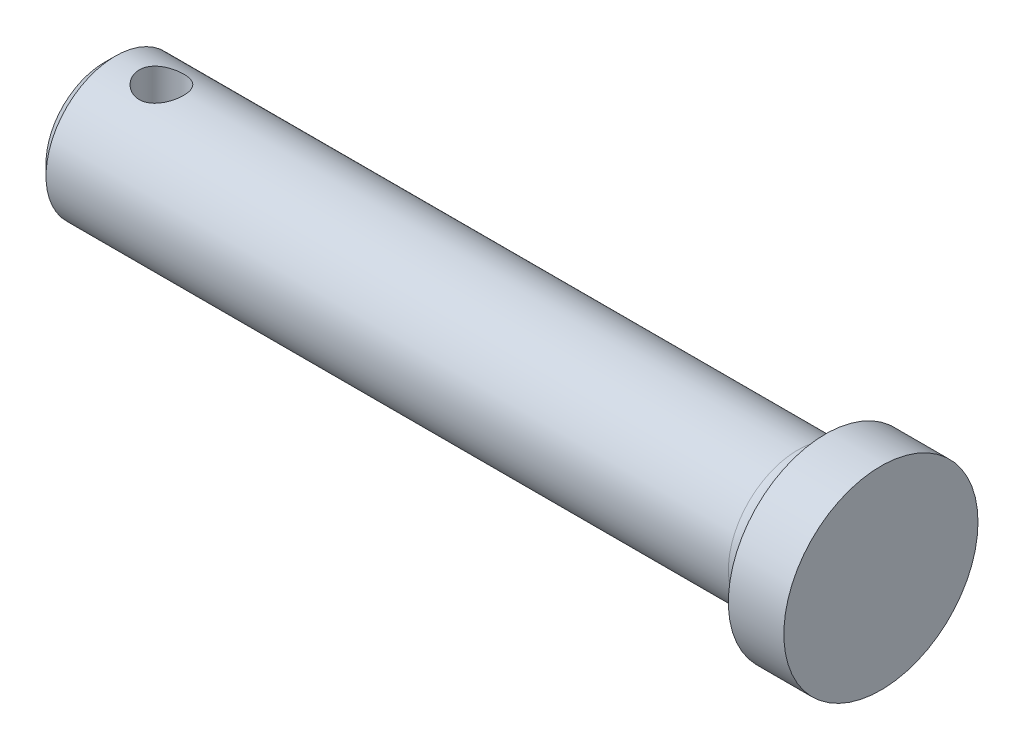
SolidWorks part; units mm, degrees
ref_plane "Front Plane" through (0, 0, 0) normal (0, 0, 1) x (1, 0, 0)
ref_plane "Top Plane" through (0, 0, 0) normal (0, 1, 0) x (1, 0, 0)
ref_plane "Right Plane" through (0, 0, 0) normal (1, 0, 0) x (0, 0, -1)
sketch "Sketch1" plane through (0, 0, 0) normal (1, 0, 0) x (0, 0, -1)
  circle A0 centre (0, 0) radius 1.25
  dimension "D1" = 2.5
extrude "Boss-Extrude1" add sketch "Sketch1" along normal blind 13
sketch "Sketch2" plane through (13, 0, 0) normal (1, 0, 0) x (0, 0, -1)
  circle A0 centre (0, 0) radius 1.75
  circle A1 centre (0, 0) radius 1.25 construction
  dimension "D1" = 0.5
extrude "Boss-Extrude2" add sketch "Sketch2" along normal blind 1
fillet "Fillet1" radius 0.5 1 edges at (13, 0, -1.25)
sketch "Sketch3" plane through (0, 0, 0) normal (0, 1, 0) x (1, 0, 0)
  line L0 (13, 0) -> (1.4303, 0) construction
  line L2 (13, 1.75) -> (13, -1.75) construction
  circle A0 centre (1.0303, 0) radius 0.4
  dimension "D2" = 0.8
  dimension "D1" = 11.5697
extrude "Cut-Extrude1" cut sketch "Sketch3" against normal through all both and the other way through all
chamfer "Chamfer1" distance 0.2 angle 45 1 edges at (0, 0, -1.25)
